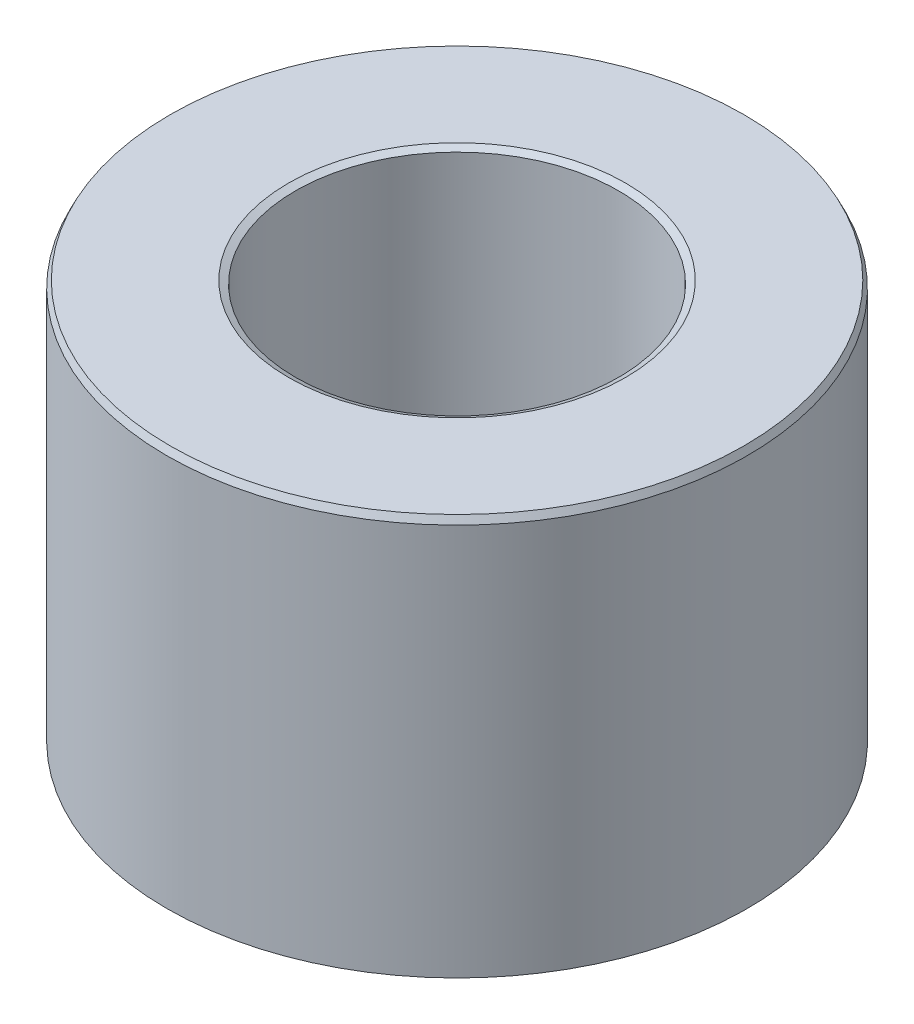
SolidWorks part; units mm, degrees
ref_plane "Front Plane" through (0, 0, 0) normal (0, 0, 1) x (1, 0, 0)
ref_plane "Top Plane" through (0, 0, 0) normal (0, 1, 0) x (1, 0, 0)
ref_plane "Right Plane" through (0, 0, 0) normal (1, 0, 0) x (0, 0, -1)
sketch "Sketch1" plane through (0, 0, 0) normal (0, 1, 0) x (1, 0, 0)
  circle A0 centre (0, 0) radius 40
  dimension "SLEEVE_OD" = 80
extrude "Boss-Extrude1" add sketch "Sketch1" along normal blind 55.4587
sketch "Sketch2" plane through (0, 0, 0) normal (0, 1, 0) x (1, 0, 0)
  circle A0 centre (0, 0) radius 22.2755
  dimension "BORE_D" = 44.5509
extrude "Cut-Extrude1" cut sketch "Sketch2" along normal through all
chamfer "Chamfer1" distance 0.9479 angle 25.57 4 edges at (0, 55.4587, 22.2755) (0, 0, 22.2755) (0, 0, 40) (0, 55.4587, 40) first distance on face at (0, 55.4587, 22.2755) first distance on face at (0, 0, 22.2755) first distance on face at (0, 55.4587, 40)
